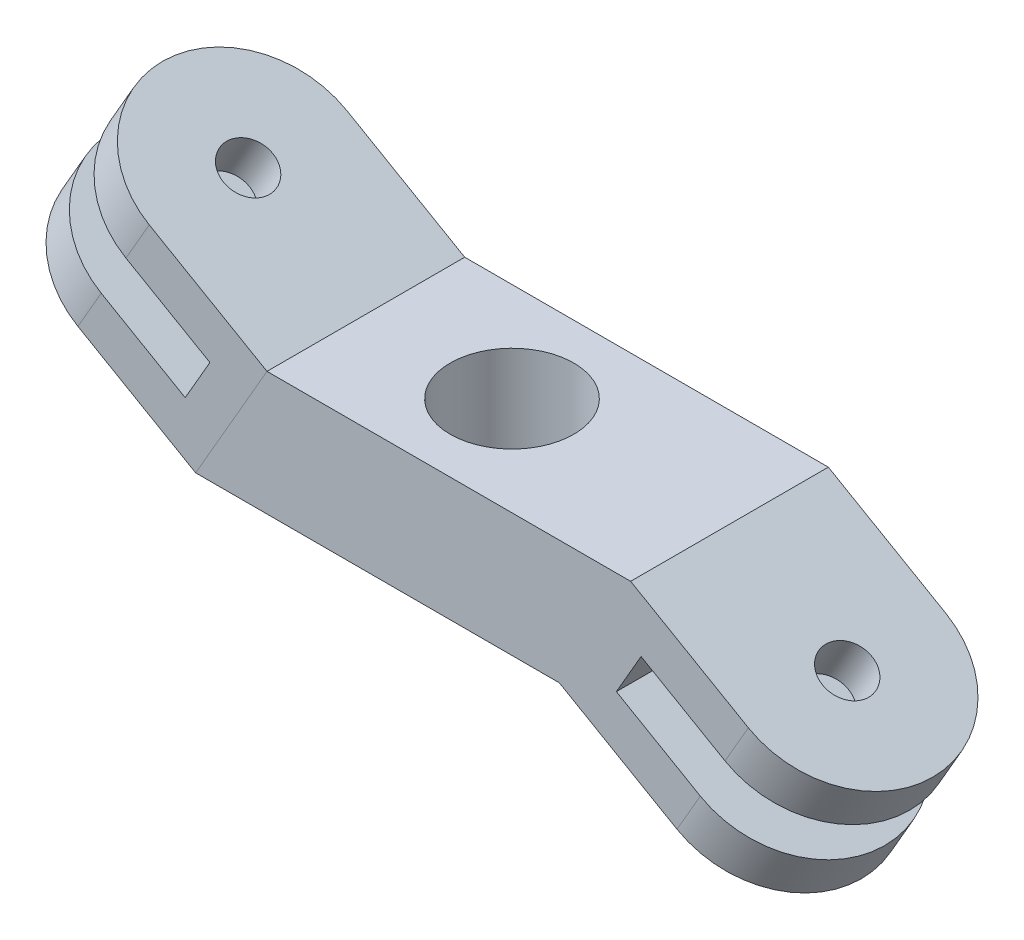
SolidWorks part; units mm, degrees
ref_plane "前视基准面" through (0, 0, 0) normal (0, 0, 1) x (1, 0, 0)
ref_plane "上视基准面" through (0, 0, 0) normal (0, 1, 0) x (1, 0, 0)
ref_plane "右视基准面" through (0, 0, 0) normal (1, 0, 0) x (0, 0, -1)
sketch "草图2" plane through (0, 0, 0) normal (0, 1, 0) x (1, 0, 0)
  circle A0 centre (0, 0) radius 6
extrude "凸台-拉伸1" add sketch "草图2" along normal blind 5
sketch "草图3" plane through (0, 5, 0) normal (0, 1, 0) x (1, 0, 0)
  circle A0 centre (0, 0) radius 2.5
extrude "切除-拉伸1" cut sketch "草图3" against normal up to surface (5 mm away) up to face at (0, 0, 6)
sketch "草图4" plane through (0, 0, 0) normal (0, 0, 1) x (1, 0, 0)
  line L0 (0, 0) -> (-3.0701, 0) construction
  line L1 (-3.0701, 0) -> (-8.7996, 0)
  line L2 (-3.0701, 0) -> (-3.0701, 5)
  line L3 (-3.0701, 5) -> (-8.7996, 5)
  line L4 (-8.7996, 0) -> (-8.7996, 5)
extrude "凸台-拉伸2" add sketch "草图4" along normal blind 4 and the other way blind 4
ref_plane "基准面4" through (-6.5997, 3.8103, 0) normal (0.866, -0.5, 0) x (0, 0, 1)
sketch "草图5" plane through (-6.5997, 3.8103, 0) normal (0.866, -0.5, 0) x (0, 0, 1)
  line L1 (-7.6932, -3.4349) -> (9.9976, -3.4349)
  line L2 (-7.6932, -3.4349) -> (-7.6932, 8.2589)
  line L3 (-7.6932, 8.2589) -> (9.9976, 8.2589)
  line L4 (9.9976, -3.4349) -> (9.9976, 8.2589)
extrude "切除-拉伸3" cut sketch "草图5" against normal blind 4.5
ref_plane "基准面5" through (0.6868, 1.1897, 0) normal (0.5, 0.866, 0) x (0, 0, 1)
sketch "草图6" plane through (0.6868, 1.1897, 0) normal (0.5, 0.866, 0) x (0, 0, 1)
  line L1 (-4, -7.6207) -> (4, -7.6207) construction
  line L5 (-4, -13.1215) -> (-4, -7.6207)
  line L6 (4, -7.6207) -> (-4, -7.6207)
  line L7 (4, -13.1215) -> (4, -7.6207)
  line L8 (0, -7.6207) -> (0, -19.8298) construction
  arc A3 (4, -13.1215) -> (-4, -13.1215) centre (0, -13.1215) cw
  point P0 (0, -7.6207)
  point P1 (-14.3488, -19.6042)
  point P10 (0, -7.6207)
extrude "凸台-拉伸3" add sketch "草图6" against normal up to vertex (5.7735 mm away) separate body up to point (-8.7996, 0, 4)
sketch "草图7" plane through (0.6868, 1.1897, 0) normal (0.5, 0.866, 0) x (0.866, -0.5, 0)
  circle A0 centre (-13.1215, 0) radius 1
extrude "切除-拉伸4" cut sketch "草图7" against normal up to surface (5.7735 mm away) up to face at (-12.0476, 1.8752, 0)
ref_plane "基准面6" through (-0.7565, -1.3103, 0) normal (0.5, 0.866, 0) x (0.866, -0.5, 0)
sketch "草图9" plane through (-0.7565, -1.3103, 0) normal (0.5, 0.866, 0) x (0.866, -0.5, 0)
  line L1 (-9.1986, 8.297) -> (-31.9565, 8.297)
  line L2 (-9.1986, 8.297) -> (-9.1986, -7.3531)
  line L3 (-9.1986, -7.3531) -> (-31.9565, -7.3531)
  line L4 (-31.9565, 8.297) -> (-31.9565, -7.3531)
extrude "切除-拉伸5" cut sketch "草图9" against normal blind 1 and the other way blind 1
mirror "镜向1" about plane through (0, 0, 0) normal (1, 0, 0) of "凸台-拉伸2"
ref_plane "基准面7" through (0, 2.5, 0) normal (0, 1, 0) x (1, 0, 0)
ref_axis "基准轴1" through (0, 2.5, -6.6) along (0, 0, 1)
pattern_circular "阵列(圆周)3" count 2 every 180 about axis through (0, 2.5, -6.6) along (0, 0, 1) of "切除-拉伸3"
ref_axis "基准轴2" through (0, 8.925, 0) along (0, -1, 0)
pattern_circular "阵列(圆周)4" count 2 every 180 about axis through (0, 2.5, -6.6) along (0, 0, 1) of "凸台-拉伸3", "切除-拉伸4", "切除-拉伸5"
sketch "草图10" plane through (0, 5, 0) normal (0, 1, 0) x (1, 0, 0)
  line L1 (4.4721, -4) -> (-5.1165, -4)
  line L2 (4.4721, -4) -> (4.4721, -8.2568)
  line L3 (4.4721, -8.2568) -> (-5.1165, -8.2568)
  line L4 (-5.1165, -4) -> (-5.1165, -8.2568)
  line L5 (4.4721, 4) -> (-4.4721, 4)
  line L6 (4.4721, 4) -> (4.4721, 8.6824)
  line L7 (4.4721, 8.6824) -> (-4.4721, 8.6824)
  line L8 (-4.4721, 4) -> (-4.4721, 8.6824)
extrude "切除-拉伸6" cut sketch "草图10" against normal blind 10
